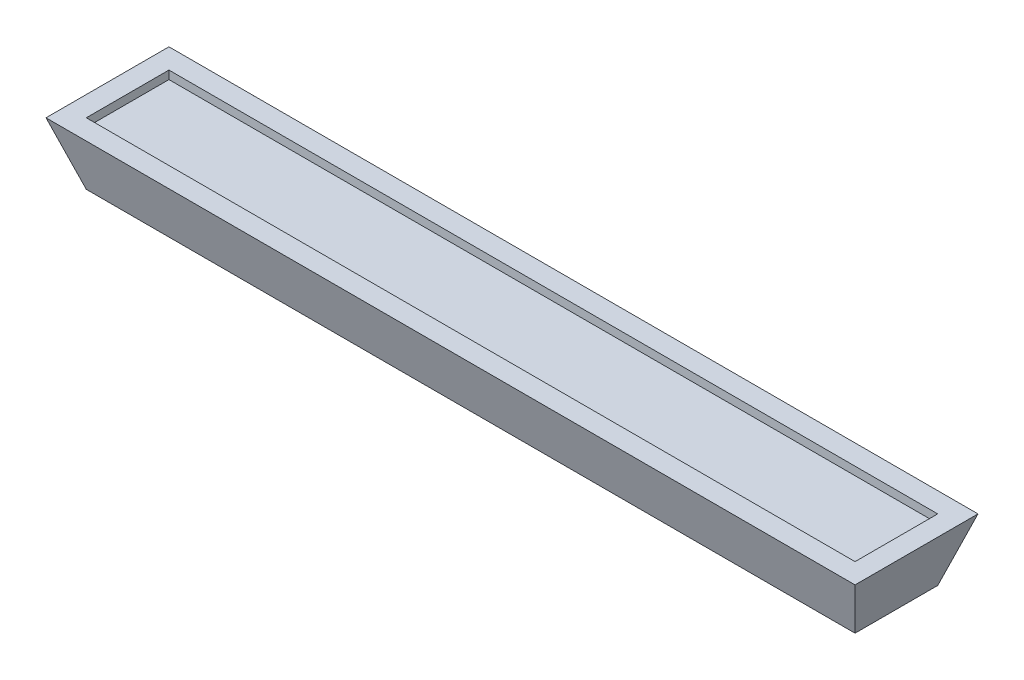
SolidWorks part; units mm, degrees
ref_plane "前视基准面" through (0, 0, 0) normal (0, 0, 1) x (1, 0, 0)
ref_plane "上视基准面" through (0, 0, 0) normal (0, 1, 0) x (1, 0, 0)
ref_plane "右视基准面" through (0, 0, 0) normal (1, 0, 0) x (0, 0, -1)
other "Configuration Table"
sketch "草图1" plane through (0, 0, 0) normal (0, 1, 0) x (1, 0, 0)
  line L1 (-93, 10) -> (93, 10)
  line L2 (-93, 10) -> (-93, -10)
  line L3 (-93, -10) -> (93, -10)
  line L4 (93, 10) -> (93, -10)
  line L5 (-93, 10) -> (93, -10) construction
  line L6 (-93, -10) -> (93, 10) construction
  point P0 (0, 0)
  dimension "D1" = 186
  dimension "D2" = 20
extrude "凸台-拉伸1" add sketch "草图1" along normal blind 15 draft 18 draft outward yes
sketch "草图2" plane through (0, 15, 0) normal (0, 1, 0) x (1, 0, 0)
  line L1 (-93, 10) -> (93, 10)
  line L2 (-93, 10) -> (-93, -10)
  line L3 (-93, -10) -> (93, -10)
  line L4 (93, 10) -> (93, -10)
  line L5 (-93, 10) -> (93, -10) construction
  line L6 (-93, -10) -> (93, 10) construction
  point P0 (0, 0)
  dimension "D1" = 186
  dimension "D2" = 20
extrude "切除-拉伸2" cut sketch "草图2" against normal blind 2
sketch "草图3" plane through (0, 0, 0) normal (0, -1, 0) x (1, 0, 0)
  line L1 (-88.5, 5.5) -> (88.5, 5.5)
  line L2 (-88.5, 5.5) -> (-88.5, -5.5)
  line L3 (-88.5, -5.5) -> (88.5, -5.5)
  line L4 (88.5, 5.5) -> (88.5, -5.5)
  line L5 (-88.5, 5.5) -> (88.5, -5.5) construction
  line L6 (-88.5, -5.5) -> (88.5, 5.5) construction
  point P0 (0, 0)
  dimension "D1" = 177
  dimension "D2" = 11
extrude "切除-拉伸3" cut sketch "草图3" against normal blind 4
sketch "草图4" plane through (0, 4, 0) normal (0, -1, 0) x (1, 0, 0)
  line L0 (0, 34.5012) -> (0, -30.2871) construction
  circle A0 centre (-72, 0) radius 2.75
  circle A1 centre (-38, 0) radius 2.75
  circle A2 centre (38, 0) radius 2.75
  circle A3 centre (72, 0) radius 2.75
  dimension "D5" = 5.5
  dimension "D6" = 5.5
  dimension "D7" = 5.5
  dimension "D8" = 5.5
  dimension "D1" = 38
  dimension "D2" = 72
  dimension "D3" = 38
  dimension "D4" = 72
extrude "切除-拉伸6" cut sketch "草图4" against normal blind 5.5
